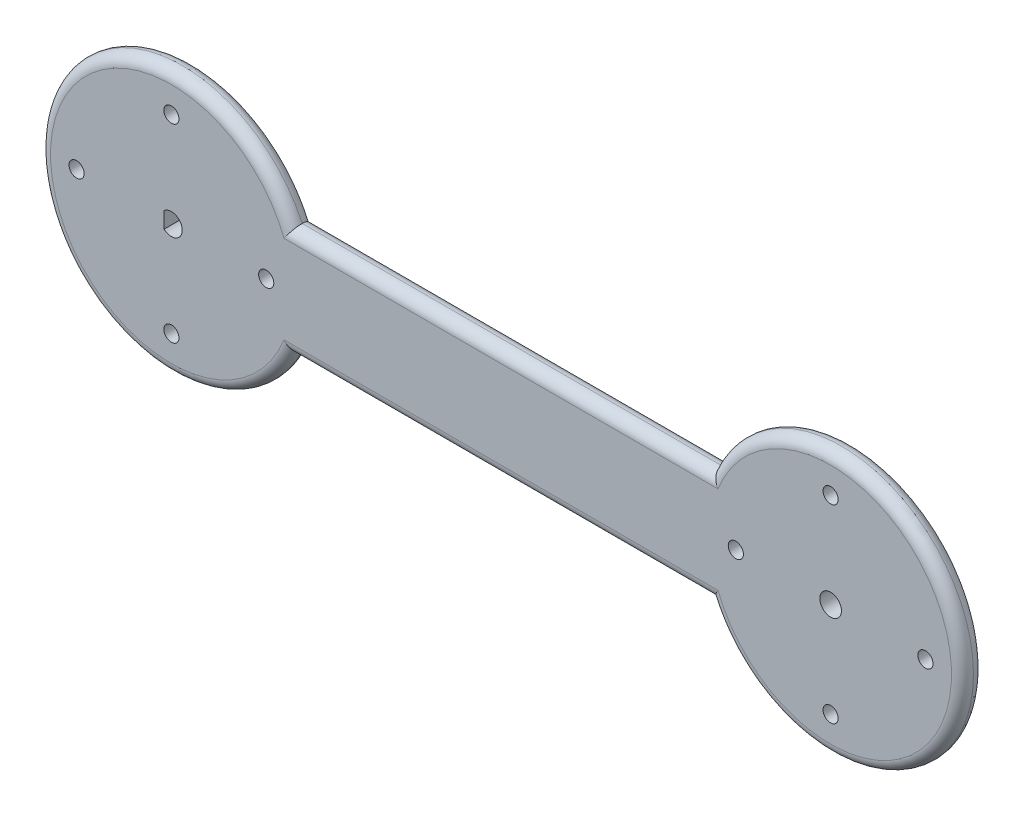
SolidWorks part; units mm, degrees
material "Plain Carbon Steel"
ref_plane "Front Plane" through (0, 0, 0) normal (0, 0, 1) x (1, 0, 0)
ref_plane "Top Plane" through (0, 0, 0) normal (0, 1, 0) x (1, 0, 0)
ref_plane "Right Plane" through (0, 0, 0) normal (1, 0, 0) x (0, 0, -1)
sketch "Sketch1" plane through (0, 0, 0) normal (0, 0, 1) x (1, 0, 0)
  line L0 (-1.6783, 1.8555) -> (-1.6783, -1.8555)
  line L1 (27.7081, -12.7) -> (124.6919, -12.7)
  line L2 (27.7081, 12.7) -> (124.6919, 12.7)
  line L3 (0, 0) -> (152.4, 0) construction
  arc A0 (-1.6783, -1.8555) -> (-1.6783, 1.8555) centre (0, 0) ccw
  arc A1 (27.7081, 12.7) -> (27.7081, -12.7) centre (0, 0) ccw
  circle A2 centre (152.4, 0) radius 2.5019
  arc A3 (124.6919, -12.7) -> (124.6919, 12.7) centre (152.4, 0) ccw
  dimension "D1" = 5.0038
  dimension "D2" = 60.96
  dimension "D4" = 60.96
  dimension "D5" = 5.0038
  dimension "D3" = 152.4
  dimension "D6" = 3.711
  dimension "D7" = 12.7
  dimension "D8" = 12.7
extrude "Boss-Extrude1" add sketch "Sketch1" along normal blind 5.08
fillet "Fillet1" radius 2.54 4 edges at (-30.48, 0, 5.08) (76.2, -12.7, 5.08) (76.2, 12.7, 5.08) (182.88, 0, 5.08)
fillet "Fillet2" radius 2.54 4 edges at (76.2, -12.7, 0) (-30.48, 0, 0) (76.2, 12.7, 0) (182.88, 0, 0)
sketch "Sketch2" plane through (0, 0, 5.08) normal (0, 0, 1) x (1, 0, 0)
  line L0 (0, 0) -> (21.9203, 0) construction
  line L1 (0, 0) -> (0, -21.9203) construction
  circle A0 centre (21.9203, 0) radius 1.75
  circle A1 centre (0, -21.9203) radius 1.75
  circle A2 centre (-21.9203, 0) radius 1.75
  circle A3 centre (0, 21.9203) radius 1.75
  arc A4 (26.0273, 10.16) -> (26.0273, -10.16) centre (0, 0) ccw construction
  arc A5 (27.7081, 12.7) -> (27.7081, -12.7) centre (0, 0) ccw construction
  dimension "D1" = 3.5
  dimension "D2" = 0
  dimension "D3" = 21.9203
  dimension "D6" = 21.9203
  dimension "D7" = 21.9203
  dimension "D5" = 90
  dimension "D4" = 4
extrude "Cut-Extrude1" cut sketch "Sketch2" against normal through all
ref_plane "Plane1" through (76.2, 0, 0) normal (1, 0, 0) x (0, 0, -1)
mirror "Mirror1" about plane through (76.2, 0, 0) normal (1, 0, 0) of "Cut-Extrude1"
